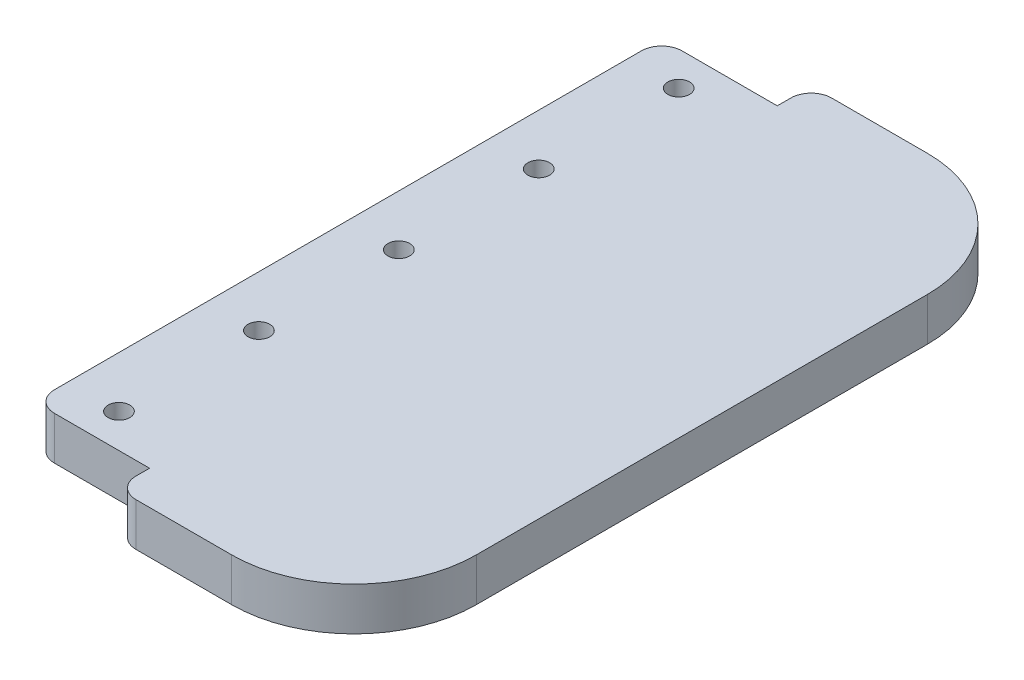
SolidWorks part; units mm, degrees
ref_plane "Front Plane" through (0, 0, 0) normal (0, 0, 1) x (1, 0, 0)
ref_plane "Top Plane" through (0, 0, 0) normal (0, 1, 0) x (1, 0, 0)
ref_plane "Right Plane" through (0, 0, 0) normal (1, 0, 0) x (0, 0, -1)
sketch "Sketch1" plane through (0, 0, 0) normal (0, 1, 0) x (1, 0, 0)
  line L0 (7.5, 102.362) -> (7.5, 0) construction
  line L1 (0, 0) -> (52.084, 0)
  line L2 (0, 0) -> (0, 102.362)
  line L3 (0, 102.362) -> (52.084, 102.362)
  line L4 (52.084, 0) -> (52.084, 102.362)
  line L6 (17, 0) -> (0, 0)
  line L7 (17, 0) -> (17, 5)
  line L8 (17, 5) -> (0, 5)
  line L9 (0, 0) -> (0, 5)
  line L10 (0, 102.362) -> (17, 102.362)
  line L11 (0, 102.362) -> (0, 97.362)
  line L12 (0, 97.362) -> (17, 97.362)
  line L13 (17, 102.362) -> (17, 97.362)
  circle A0 centre (38.876, 95.63) radius 3.556
  circle A1 centre (38.876, 51.18) radius 11.684
  circle A2 centre (38.876, 6.73) radius 3.556
  circle A3 centre (7.5, 92.362) radius 1.6
  circle A4 centre (7.5, 71.772) radius 1.6
  circle A5 centre (7.5, 51.182) radius 1.6
  circle A6 centre (7.5, 30.592) radius 1.6
  circle A7 centre (7.5, 10.002) radius 1.6
  dimension "D3" = 7.112
  dimension "D4" = 7.112
  dimension "D5" = 23.368
  dimension "D11" = 3.2
  dimension "D1" = 102.362
  dimension "D2" = 52.084
  dimension "D6" = 44.45
  dimension "D7" = 44.45
  dimension "D8" = 51.18
  dimension "D9" = 13.208
  dimension "D10" = 7.5
  dimension "D12" = 10
  dimension "D14" = 17
  dimension "D15" = 5
  dimension "D16" = 17
  dimension "D17" = 5
  dimension "D18" = 20.59
  dimension "D13" = 5
extrude "Boss-Extrude1" add sketch "Sketch1" along normal blind 6.35 contours L1 L4 L3 L2
extrude "Cut-Extrude2" cut sketch "Sketch1<4>" along normal through all contours A4 L0 | L0 A4 | A3 | A5 | A6 | A7 region at (8.1791, 0, -71.772) region at (6.8209, 0, -71.772)
sketch "Sketch1<4>" plane through (0, 0, 0) normal (0, 1, 0) x (1, 0, 0) same geometry as "Sketch1"
extrude "Cut-Extrude3" cut sketch "Sketch1<5>" along normal offset from surface (4.7625 mm away) 1.5875 contours A1 | A0 | A2 region at (38.876, 0, -95.63) region at (38.876, 0, -51.18) up to face at (7.5, 6.35, -8.402)
sketch "Sketch1<5>" plane through (0, 0, 0) normal (0, 1, 0) x (1, 0, 0) same geometry as "Sketch1"
fillet "Fillet1" radius 18 2 edges at (52.084, 3.175, -102.362) (52.084, 3.175, 0)
extrude "Cut-Extrude4" cut sketch "Sketch1<7>" along normal through all contours L6 L7 L8 L9 | L10 L13 L12 L11
sketch "Sketch1<7>" plane through (0, 0, 0) normal (0, 1, 0) x (1, 0, 0) same geometry as "Sketch1"
fillet "Fillet4" radius 3 4 edges at (17, 3.175, -102.362) (0, 3.175, -97.362) (0, 3.175, -5) (17, 3.175, 0)
